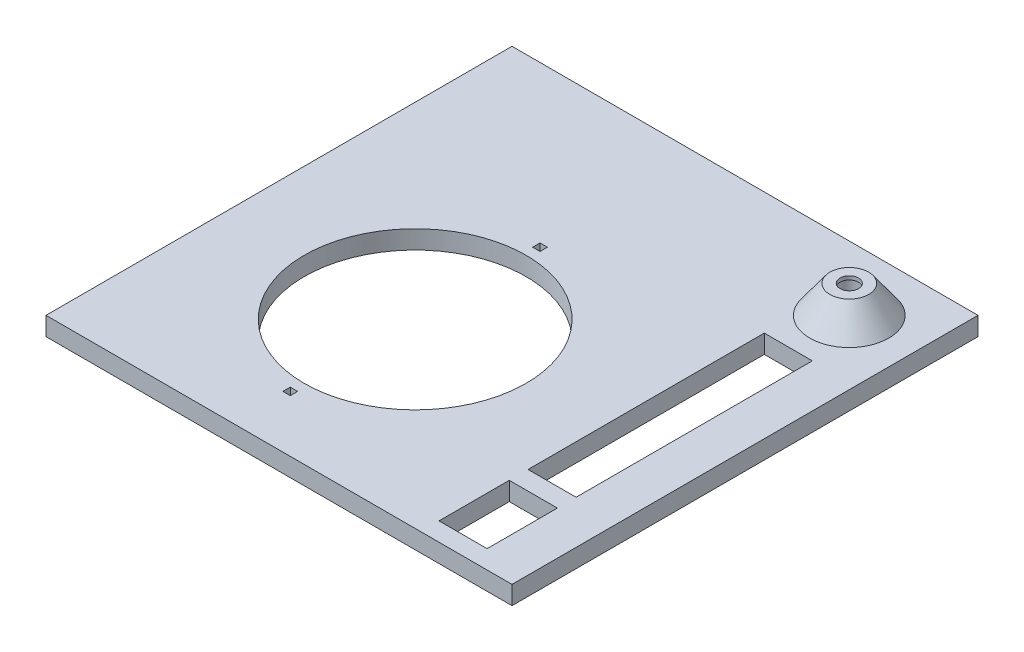
SolidWorks part; units mm, degrees
ref_plane "Front Plane" through (0, 0, 0) normal (0, 0, 1) x (1, 0, 0)
ref_plane "Top Plane" through (0, 0, 0) normal (0, 1, 0) x (1, 0, 0)
ref_plane "Right Plane" through (0, 0, 0) normal (1, 0, 0) x (0, 0, -1)
sketch "Sketch1" plane through (0, 0, 0) normal (0, 1, 0) x (1, 0, 0)
  line L1 (0, 0) -> (126, 0)
  line L2 (0, 0) -> (0, 126)
  line L3 (0, 126) -> (126, 126)
  line L4 (126, 0) -> (126, 126)
  dimension "D1" = 126
  dimension "D2" = 126
extrude "Boss-Extrude1" add sketch "Sketch1" along normal blind 5
sketch "Sketch3" plane through (0, 5, 0) normal (0, 1, 0) x (1, 0, 0)
  line L0 (108.6, 121.1) -> (108.6, 96.1) construction
  circle A0 centre (108.6, 108.6) radius 12.5
extrude "Boss-Extrude2" add sketch "Sketch3" along normal blind 7.5
sketch "Sketch4" plane through (0, 0, 0) normal (0, -1, 0) x (1, 0, 0)
  circle A1 centre (108.6, -108.6) radius 2.95
  dimension "D1" = 5.9
extrude "Cut-Extrude1" cut sketch "Sketch4" against normal blind 11.5
sketch "Sketch6" plane through (0, 12.5, 0) normal (0, 1, 0) x (1, 0, 0)
  line L0 (108.6, 121.1) -> (108.6, 96.1) construction
  circle A0 centre (108.6, 108.6) radius 12.5 construction
  circle A1 centre (108.6, 108.6) radius 2.5
  dimension "D1" = 5
extrude "Cut-Extrude2" cut sketch "Sketch6" against normal through all
chamfer "Chamfer1" distance 10 angle 36 1 edges at (108.6, 12.5, -96.1) first distance on face at (108.6, 12.5, -96.1)
sketch "Sketch8" plane through (0, 5, 0) normal (0, 1, 0) x (1, 0, 0)
  line L7 (114.2633, 24) -> (101.2633, 24)
  line L8 (114.2633, 24) -> (114.2633, 5)
  line L9 (114.2633, 5) -> (101.2633, 5)
  line L10 (101.2633, 24) -> (101.2633, 5)
  line L11 (114.2633, 24) -> (101.2633, 5) construction
  line L12 (114.2633, 5) -> (101.2633, 24) construction
  line L13 (114.2633, 24) -> (101.2633, 24)
  line L21 (114.2633, 29.0695) -> (101.2633, 29.0695)
  line L22 (114.2633, 29.0695) -> (114.2633, 92.9492)
  line L23 (114.2633, 92.9492) -> (101.2633, 92.9492)
  line L24 (101.2633, 29.0695) -> (101.2633, 92.9492)
  line L25 (114.2633, 29.0695) -> (101.2633, 92.9492) construction
  line L26 (114.2633, 92.9492) -> (101.2633, 29.0695) construction
  point P11 (107.7633, 14.5)
  point P17 (107.7633, 61.0093)
  dimension "D2" = 13
  dimension "D3" = 19
extrude "Cut-Extrude3" cut sketch "Sketch8" against normal through all contours L24 L21 L22 L23 | L7 L10 L9 L8 region at (107.7633, 5, -14.5) region at (107.7633, 5, -61.0093)
sketch "Sketch9" plane through (0, 5, 0) normal (0, 1, 0) x (1, 0, 0)
  circle A0 centre (50.8372, 48.9746) radius 30
  dimension "D1" = 60
extrude "Cut-Extrude4" cut sketch "Sketch9" against normal through all
sketch "Sketch10" plane through (0, 5, 0) normal (0, 1, 0) x (1, 0, 0)
  line L0 (50.8372, 78.9746) -> (50.8372, 18.9746) construction
  line L2 (18.3372, 67.7385) -> (18.3372, 30.2107)
  line L3 (18.3372, 30.2107) -> (50.8372, 11.4468)
  line L4 (50.8372, 11.4468) -> (83.3372, 30.2107)
  line L5 (83.3372, 30.2107) -> (83.3372, 67.7385)
  line L6 (83.3372, 67.7385) -> (50.8372, 86.5024)
  line L7 (50.8372, 86.5024) -> (18.3372, 67.7385)
  circle A0 centre (50.8372, 48.9746) radius 30 construction
  circle A1 centre (50.8372, 48.9746) radius 32.5 construction
  dimension "D1" = 65
sketch "Sketch11" plane through (0, 5, 0) normal (0, 1, 0) x (1, 0, 0)
  line L0 (50.8372, 78.9746) -> (50.8372, 86.5024) construction
  line L1 (50.8372, 11.4468) -> (50.8372, 18.9746) construction
  line L2 (51.8372, 83.7385) -> (49.8372, 83.7385)
  line L3 (51.8372, 83.7385) -> (51.8372, 81.7385)
  line L4 (51.8372, 81.7385) -> (49.8372, 81.7385)
  line L5 (49.8372, 83.7385) -> (49.8372, 81.7385)
  line L6 (51.8372, 83.7385) -> (49.8372, 81.7385) construction
  line L7 (51.8372, 81.7385) -> (49.8372, 83.7385) construction
  line L9 (51.8372, 14.2107) -> (49.8372, 14.2107)
  line L10 (51.8372, 14.2107) -> (51.8372, 16.2107)
  line L11 (51.8372, 16.2107) -> (49.8372, 16.2107)
  line L12 (49.8372, 14.2107) -> (49.8372, 16.2107)
  line L13 (51.8372, 14.2107) -> (49.8372, 16.2107) construction
  line L14 (51.8372, 16.2107) -> (49.8372, 14.2107) construction
  point P4 (50.8372, 82.7385)
  point P13 (50.8372, 15.2107)
  dimension "D1" = 2
  dimension "D2" = 2
  dimension "D3" = 2
  dimension "D4" = 2
extrude "Cut-Extrude5" cut sketch "Sketch11" against normal blind 3
sketch "Sketch13" plane through (0, 5, 0) normal (0, 1, 0) x (1, 0, 0)
  line L1 (126, 126) -> (0, 126) construction
  line L2 (50.8372, 126) -> (50.8372, 0) construction
  line L3 (0, 0) -> (126, 0) construction
  line L4 (0, 126) -> (0, 0) construction
  line L5 (0, 86.5024) -> (126, 86.5024) construction
  line L6 (126, 0) -> (126, 126) construction
  line L7 (18.3372, 126) -> (18.3372, 0) construction
  line L9 (83.3372, 126) -> (83.3372, 0) construction
